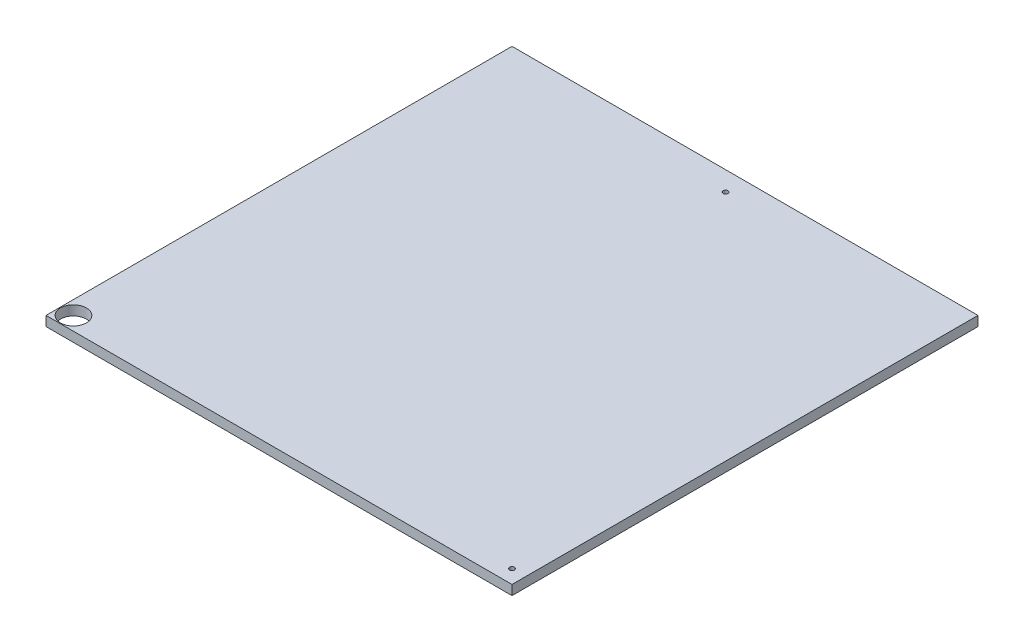
SolidWorks part; units mm, degrees
material "Cedar"
ref_plane "Front Plane" through (0, 0, 0) normal (0, 0, 1) x (1, 0, 0)
ref_plane "Top Plane" through (0, 0, 0) normal (0, 1, 0) x (1, 0, 0)
ref_plane "Right Plane" through (0, 0, 0) normal (1, 0, 0) x (0, 0, -1)
sketch "Sketch1" plane through (0, 0, 0) normal (0, 1, 0) x (1, 0, 0)
  line L1 (0, 0) -> (609.6, 0)
  line L2 (0, 0) -> (0, 609.6)
  line L3 (0, 609.6) -> (609.6, 609.6)
  line L4 (609.6, 0) -> (609.6, 609.6)
  dimension "D1" = 609.6
  dimension "D2" = 609.6
extrude "Boss-Extrude1" add sketch "Sketch1" along normal blind 12.7
sketch "Sketch5" plane through (0, 12.7, 0) normal (0, 1, 0) x (1, 0, 0)
  line L0 (304.8, 609.6) -> (304.8, 584.2) construction
  line L1 (609.6, 609.6) -> (0, 609.6) construction
  line L2 (0, 0) -> (17.9605, 17.9605) construction
  line L3 (609.6, 0) -> (591.6395, 17.9605) construction
  line L4 (0, 0) -> (609.6, 0) construction
  circle A0 centre (17.9605, 17.9605) radius 3.175
  circle A1 centre (591.6395, 17.9605) radius 3.175
  circle A2 centre (304.8, 584.2) radius 3.175
  dimension "D6" = 6.35
  dimension "D7" = 6.35
  dimension "D8" = 6.35
  dimension "D1" = 25.4
  dimension "D2" = 45
  dimension "D3" = 25.4
  dimension "D4" = 45
  dimension "D5" = 25.4
extrude "Cut-Extrude2" cut sketch "Sketch5" against normal through all
sketch "Sketch6" plane through (0, 12.7, 0) normal (0, 1, 0) x (1, 0, 0)
  line L0 (0, 609.6) -> (609.6, 0) construction
  line L1 (609.6, 609.6) -> (0, 0) construction
  point P8 (304.8, 304.8)
sketch "Sketch7" plane through (0, 12.7, 0) normal (0, 1, 0) x (1, 0, 0)
  circle A0 centre (17.9605, 17.9605) radius 17
extrude "Cut-Extrude3" cut sketch "Sketch7" against normal through all
